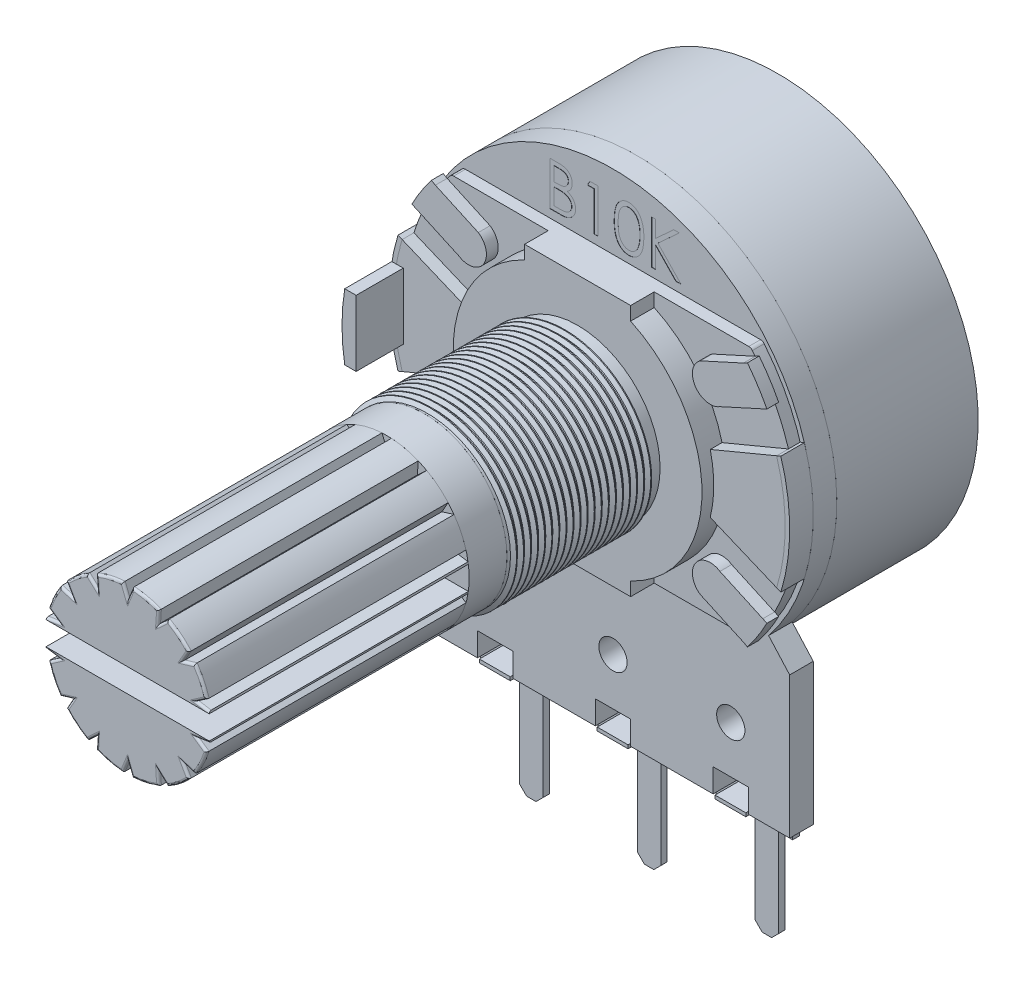
SolidWorks part; units mm, degrees
ref_plane "Alzado" through (0, 0, 0) normal (0, 0, 1) x (1, 0, 0)
ref_plane "Planta" through (0, 0, 0) normal (0, 1, 0) x (1, 0, 0)
ref_plane "Vista lateral" through (0, 0, 0) normal (1, 0, 0) x (0, 0, -1)
sketch "Croquis1" plane through (0, 0, 0) normal (0, 0, 1) x (1, 0, 0)
  circle A0 centre (0, 0) radius 8.5
  dimension "D1" = 17
extrude "Saliente-Extruir1" add sketch "Croquis1" along normal blind 6
sketch "Croquis2" plane through (0, 0, 0) normal (0, 0, -1) x (-1, 0, 0)
  line L0 (0, 0) -> (0, 8.5) construction
  line L1 (0, 0) -> (9.791, 0) construction
  line L2 (6.941, 1) -> (6.941, -1)
  line L3 (6.941, 1) -> (8.441, 1)
  line L4 (6.941, -1) -> (8.441, -1)
  circle A0 centre (0, 0) radius 8.5 construction
  arc A1 (8.441, 1) -> (8.441, -1) centre (0, 0) cw
  point P12 (6.941, 0)
  dimension "D1" = 1
  dimension "D2" = 1.5
extrude "Cortar-Extruir1" cut sketch "Croquis2" against normal blind 3 contours A1 L4 L2 L3
ref_plane "Plano1" through (0, -8.5, 0) normal (0, 1, 0) x (1, 0, 0)
sketch "Croquis3" plane through (0, -8.5, 0) normal (0, 1, 0) x (1, 0, 0)
  line L0 (0, 0) -> (0, -4.2789) construction
  line L1 (0, -4.2789) -> (0, -6) construction
  line L2 (-8.5, -6) -> (8.5, -6) construction
  line L3 (5.5, -3.5) -> (-5.5, -3.5)
  line L4 (-5.5, -3.5) -> (-5.5, -6)
  line L5 (-5.5, -6) -> (5.5, -6)
  line L6 (5.5, -3.5) -> (5.5, -6)
  point P11 (0, -3.5)
  dimension "D1" = 5.5
  dimension "D2" = 2.5
extrude "Cortar-Extruir2" cut sketch "Croquis3" along normal blind 5
sketch "Croquis4" plane through (0, 0, 6) normal (0, 0, 1) x (1, 0, 0)
  line L0 (-7.5, -12.3514) -> (7.5, -12.3514)
  line L1 (7.5, -12.3514) -> (7.5, -6.3514)
  line L2 (-7.5, -12.3514) -> (-7.5, -6.3514)
  line L3 (0, 0) -> (0, -14.8368) construction
  line L5 (6.604, -5.3514) -> (7.5, -6.3514)
  line L7 (-6.604, -5.3514) -> (-7.5, -6.3514)
  arc A0 (6.604, -5.3514) -> (-6.604, -5.3514) centre (0, 0) ccw
  arc A1 (5.5, -6.4807) -> (-5.5, -6.4807) centre (0, 0) ccw construction
  point P11 (0, -12.3514)
  dimension "D1" = 6
  dimension "D2" = 7.5
  dimension "D3" = 7
extrude "Saliente-Extruir2" add sketch "Croquis4" along normal blind 1 separate body
sketch "Croquis5" plane through (0, 0, 7) normal (0, 0, 1) x (1, 0, 0)
  line L0 (6.2625, -5.3514) -> (-6.2625, -5.3514)
  line L1 (0, 0) -> (4.67, 0) construction
  line L2 (6.2625, 5.3514) -> (-6.2625, 5.3514)
  line L3 (0, 8.5) -> (6.3562, 8.5) construction
  line L5 (0, 0) -> (0, 6.7087) construction
  line L6 (0, 0) -> (0, -6.9451) construction
  arc A1 (6.4169, 5.2784) -> (6.4169, -5.2784) centre (0, 0) cw
  arc A2 (6.4169, 5.2784) -> (6.2625, 5.3514) centre (6.2625, 5.1514) ccw
  arc A3 (6.2625, -5.3514) -> (6.4169, -5.2784) centre (6.2625, -5.1514) ccw
  arc A4 (-6.4169, 5.2784) -> (-6.2625, 5.3514) centre (-6.2625, 5.1514) cw
  arc A5 (-6.2625, -5.3514) -> (-6.4169, -5.2784) centre (-6.2625, -5.1514) cw
  arc A6 (-6.4169, 5.2784) -> (-6.4169, -5.2784) centre (0, 0) ccw
  point P9 (0, 5.3514)
  point P27 (0, -5.3514)
  dimension "D1" = 0.2
  dimension "D2" = 0.2
extrude "Saliente-Extruir3" add sketch "Croquis5" along normal blind 0.5 separate body
sketch "Croquis6" plane through (0, 0, 7.5) normal (0, 0, 1) x (1, 0, 0)
  line L0 (0, 0) -> (0, 6.118) construction
  line L1 (0, 0) -> (2.5948, 0) construction
  line L2 (8.124, -2.5) -> (5.1285, -1.25)
  line L6 (5.2787, 0) -> (8.5, 0)
  line L7 (8.124, 2.5) -> (5.1285, 1.25)
  line L8 (-8.124, -2.5) -> (-5.1285, -1.25)
  line L9 (-8.124, 2.5) -> (-5.1285, 1.25)
  arc A1 (6.604, -5.3514) -> (-6.604, -5.3514) centre (0, 0) ccw construction
  arc A3 (8.124, 2.5) -> (8.124, -2.5) centre (0, 0) cw
  arc A4 (-8.124, 2.5) -> (-8.124, -2.5) centre (0, 0) ccw
  arc A5 (5.1285, -1.25) -> (5.1285, 1.25) centre (0, 0) ccw
  arc A6 (-5.1285, -1.25) -> (-5.1285, 1.25) centre (0, 0) cw
  point P4 (5.1285, 0)
  arc M17 (6.4169, -5.2784) -> (6.4169, 5.2784) centre (0, 0) ccw
  arc M21 (-6.4169, 5.2784) -> (-6.4169, -5.2784) centre (0, 0) ccw
  dimension "D2" = 1.25
extrude "Saliente-Extruir4" add sketch "Croquis6" along normal blind 0.5 contours L9 L8 M21 | A5 L6 L7 M17 | A5 L2 L6 M17 region at (6.8677, -0.9571, 7.5) region at (6.8677, 0.9571, 7.5) region at (-6.8677, 0, 7.5)
sketch "Croquis7" plane through (0, 0, 7.5) normal (0, 0, 1) x (1, 0, 0)
  line L0 (0, 5.2787) -> (0, 5.8858) construction
  line L1 (-2.25, 5.3514) -> (2.25, 5.3514)
  line L2 (6.2625, 5.3514) -> (-6.2625, 5.3514) construction
  line L3 (2.25, 5.3514) -> (2.25, 4.7751)
  line L4 (0, 0) -> (0, 3.5555) construction
  line L5 (0, 0) -> (2.9172, 0) construction
  line L6 (-2.25, 5.3514) -> (-2.25, 4.7751)
  line L7 (-2.25, -5.3514) -> (2.25, -5.3514)
  line L8 (2.25, -5.3514) -> (2.25, -4.7751)
  line L9 (-2.25, -5.3514) -> (-2.25, -4.7751)
  arc A0 (-2.25, 4.7751) -> (-2.25, -4.7751) centre (0, 0) ccw
  arc A1 (2.25, -4.7751) -> (2.25, 4.7751) centre (0, 0) ccw
  point P13 (0, 5.3514)
  dimension "D1" = 2.25
extrude "Saliente-Extruir5" add sketch "Croquis7" along normal blind 1
sketch "Croquis8" plane through (0, 0, 7) normal (0, 0, 1) x (1, 0, 0)
  line L0 (0, -5.3514) -> (0, -10.1607) construction
  line L1 (-2.25, -5.3514) -> (2.25, -5.3514) construction
  line L2 (7.5, -9.3514) -> (-1.2858, -9.3514) construction
  line L3 (7.5, -12.3514) -> (7.5, -6.3514) construction
  circle A0 centre (0, -9.3514) radius 0.6
  circle A1 centre (5, -9.3514) radius 0.6
  circle A2 centre (-5, -9.3514) radius 0.6
  dimension "D1" = 1.2
  dimension "D2" = 2
  dimension "D3" = 2
extrude "Cortar-Extruir3" cut sketch "Croquis8" against normal blind 5
sketch "Croquis10" plane through (0, 0, 6) normal (0, 0, -1) x (-1, 0, 0)
  line L0 (0, -12.3514) -> (0, -6.0291) construction
  line L1 (7.5, -12.3514) -> (-7.5, -12.3514) construction
  line L2 (1.625, -9.3514) -> (1.625, -13.3514)
  line L3 (1.625, -13.3514) -> (1.125, -13.3514)
  line L4 (1.125, -13.3514) -> (0.8288, -13.2473)
  line L5 (-1.125, -13.3514) -> (-0.8288, -13.2473)
  line L6 (-1.625, -13.3514) -> (-1.125, -13.3514)
  line L7 (-1.625, -9.3514) -> (-1.625, -13.3514)
  line L8 (0, -9.3514) -> (0.815, -9.3514) construction
  line L21 (6.625, -9.3514) -> (6.625, -13.3514)
  line L22 (6.625, -13.3514) -> (6.125, -13.3514)
  line L23 (6.125, -13.3514) -> (5.8288, -13.2473)
  line L24 (3.875, -13.3514) -> (4.1712, -13.2473)
  line L25 (3.375, -13.3514) -> (3.875, -13.3514)
  line L26 (3.375, -9.3514) -> (3.375, -13.3514)
  line L27 (-3.375, -9.3514) -> (-3.375, -13.3514)
  line L28 (-3.375, -13.3514) -> (-3.875, -13.3514)
  line L29 (-3.875, -13.3514) -> (-4.1712, -13.2473)
  line L30 (-6.125, -13.3514) -> (-5.8288, -13.2473)
  line L31 (-6.625, -13.3514) -> (-6.125, -13.3514)
  line L32 (-6.625, -9.3514) -> (-6.625, -13.3514)
  arc A0 (-1.625, -9.3514) -> (1.625, -9.3514) centre (0, -9.3757) cw
  arc A1 (0.8288, -13.2473) -> (-0.8288, -13.2473) centre (0, -15.6059) ccw
  circle A9 centre (5, -9.3514) radius 0.6
  circle A10 centre (0, -9.3514) radius 0.6
  arc A11 (3.375, -9.3514) -> (6.625, -9.3514) centre (5, -9.3757) cw
  arc A12 (5.8288, -13.2473) -> (4.1712, -13.2473) centre (5, -15.6059) ccw
  arc A14 (-6.625, -9.3514) -> (-3.375, -9.3514) centre (-5, -9.3757) cw
  arc A15 (-4.1712, -13.2473) -> (-5.8288, -13.2473) centre (-5, -15.6059) ccw
  circle A16 centre (-5, -9.3514) radius 0.6
  point P17 (0, -12.9561)
  dimension "D4" = 2.5
  dimension "D1" = 2
  dimension "D2" = 0.5
  dimension "D3" = 1
  dimension "D5" = 2
  dimension "D6" = 2
extrude "Saliente-Extruir6" add sketch "Croquis10" along normal blind 0.3 separate body
sketch "Croquis11" plane through (0, 0, 0) normal (1, 0, 0) x (0, 0, -1)
  line L0 (-5.7, -12.9252) -> (-5.4, -12.9252)
  line L1 (-5.2, -13.1252) -> (-5.2, -17.9252)
  line L3 (-5.7, -12.9252) -> (-5.7, -13.1042)
  line L5 (-5.7, -13.1042) -> (-5.6655, -13.1042)
  line L6 (-5.4655, -13.3042) -> (-5.4655, -17.9252)
  line L7 (-5.4655, -17.9252) -> (-5.2, -17.9252)
  arc A0 (-5.6655, -13.1042) -> (-5.4655, -13.3042) centre (-5.6655, -13.3042) cw
  arc A1 (-5.2, -13.1252) -> (-5.4, -12.9252) centre (-5.4, -13.1252) ccw
  point P12 (-5.2, -12.9252)
  dimension "D3" = 0.2
  dimension "D1" = 5
  dimension "D2" = 0.5
extrude "Saliente-Extruir7" add sketch "Croquis11" along normal blind 0.5 and the other way blind 0.5
pattern_linear "MatrizL1" count 2 spacing 5 along (1, 0, 0) of "Saliente-Extruir7"
pattern_linear "MatrizL2" count 2 spacing 5 along (-1, 0, 0) of "Saliente-Extruir7"
chamfer "Chaflán1" distance 0.3 angle 45 2 edges at (4.5, -17.9252, 5.3328) (5.5, -17.9252, 5.3328)
chamfer "Chaflán2" distance 0.3 angle 45 2 edges at (-0.5, -17.9252, 5.3328) (0.5, -17.9252, 5.3328)
chamfer "Chaflán3" distance 0.3 angle 45 2 edges at (-4.5, -17.9252, 5.3328) (-5.5, -17.9252, 5.3328)
sketch "Croquis12" plane through (0, 0, 7) normal (0, 0, 1) x (1, 0, 0)
  line L0 (0, -12.3514) -> (0, -6.5599) construction
  line L1 (-7.5, -12.3514) -> (7.5, -12.3514) construction
  line L2 (-0.75, -11.3514) -> (0.75, -11.3514)
  line L3 (0.75, -11.3514) -> (0.75, -12.3514)
  line L4 (-0.75, -11.3514) -> (-0.75, -12.3514)
  line L5 (-0.75, -12.3514) -> (0.75, -12.3514)
  line L6 (4.25, -12.3514) -> (5.75, -12.3514)
  line L7 (5.75, -11.3514) -> (5.75, -12.3514)
  line L8 (4.25, -11.3514) -> (5.75, -11.3514)
  line L9 (4.25, -11.3514) -> (4.25, -12.3514)
  line L10 (-5.75, -12.3514) -> (-4.25, -12.3514)
  line L11 (-4.25, -11.3514) -> (-4.25, -12.3514)
  line L12 (-5.75, -11.3514) -> (-4.25, -11.3514)
  line L13 (-5.75, -11.3514) -> (-5.75, -12.3514)
  point P10 (0, -11.3514)
  dimension "D1" = 0.75
  dimension "D2" = 1
  dimension "D3" = 2
  dimension "D4" = 2
extrude "Cortar-Extruir4" cut sketch "Croquis12" against normal through all
sketch "Croquis13" plane through (0, 0, 6) normal (0, 0, 1) x (1, 0, 0)
  line L0 (4.25, -12.3514) -> (4.25, -11.3514)
  line L1 (4.25, -11.3514) -> (5.75, -11.3514)
  line L2 (5.75, -11.3514) -> (5.75, -12.3514)
  line L3 (5.75, -12.3514) -> (4.25, -12.3514)
  line L4 (0.75, -12.3514) -> (-0.75, -12.3514)
  line L5 (-0.75, -12.3514) -> (-0.75, -11.3514)
  line L6 (-0.75, -11.3514) -> (0.75, -11.3514)
  line L7 (0.75, -11.3514) -> (0.75, -12.3514)
  line L8 (-4.25, -12.3514) -> (-5.75, -12.3514)
  line L9 (-5.75, -12.3514) -> (-5.75, -11.3514)
  line L10 (-5.75, -11.3514) -> (-4.25, -11.3514)
  line L11 (-4.25, -11.3514) -> (-4.25, -12.3514)
  dimension "D1" = 3
extrude "Cortar-Extruir5" cut sketch "Croquis13" against normal blind 2
sketch "Croquis14" plane through (0, 0, 6) normal (0, 0, 1) x (1, 0, 0)
  line L0 (4.3314, -12.3514) -> (5.6395, -12.3514)
  line L1 (4.25, -12.3514) -> (5.75, -12.3514) construction
  line L2 (5.6395, -12.3514) -> (5.6395, -12.4982)
  line L3 (5.6395, -12.4982) -> (4.3314, -12.4982)
  line L4 (4.3314, -12.4982) -> (4.3314, -12.3514)
  line L5 (-0.6686, -12.4982) -> (-0.6686, -12.3514)
  line L6 (-0.6686, -12.3514) -> (0.6395, -12.3514)
  line L7 (0.6395, -12.3514) -> (0.6395, -12.4982)
  line L8 (0.6395, -12.4982) -> (-0.6686, -12.4982)
  line L9 (-5.6686, -12.4982) -> (-5.6686, -12.3514)
  line L10 (-5.6686, -12.3514) -> (-4.3605, -12.3514)
  line L11 (-4.3605, -12.3514) -> (-4.3605, -12.4982)
  line L12 (-4.3605, -12.4982) -> (-5.6686, -12.4982)
  dimension "D1" = 3
extrude "Saliente-Extruir8" add sketch "Croquis14" along normal blind 1
sketch "Croquis18" plane through (0, 0, 7.5) normal (0, 0, 1) x (1, 0, 0)
  line L0 (0, 0) -> (12.103, 0) construction
  line L1 (7.3598, -3.8564) -> (5.5397, -3.0275)
  line L2 (6.5371, -5.1289) -> (4.7169, -4.3)
  line L3 (7.3598, -3.8564) -> (7.5336, -3.9364)
  line L4 (6.5371, -5.1289) -> (6.7063, -5.2226)
  arc A0 (6.4169, -5.2784) -> (7.9469, -2.4261) centre (0, 0) ccw construction
  arc A1 (5.5397, -3.0275) -> (4.7169, -4.3) centre (5.1283, -3.6637) ccw
  arc A2 (6.604, -5.3514) -> (-6.604, -5.3514) centre (0, 0) ccw construction
  arc A3 (7.5336, -3.9364) -> (6.7063, -5.2226) centre (0, 0) cw
  dimension "D1" = 2
  dimension "D2" = 1.499
extrude "Saliente-Extruir9" add sketch "Croquis18" along normal blind 0.5
mirror "Simetría2" about plane through (0, 0, 0) normal (0, 1, 0) of "Saliente-Extruir9"
mirror "Simetría3" about plane through (0, 0, 0) normal (1, 0, 0) of "Simetría2"
sketch "Croquis19" plane through (0, 0, 8.5) normal (0, 0, 1) x (1, 0, 0)
  circle A0 centre (0, 0) radius 3.5
  dimension "D1" = 7
extrude "Saliente-Extruir10" add sketch "Croquis19" along normal blind 6.5
thread "Rosca1" pitch 0.3 method extrude profile "Perfil de rosca1" start angle 0, offset 0, length 6, pitch 0.3, diameter 7
ref_plane "Plano3" through (-3.5, 0, 15) normal (0, -1, 0) x (-1, 0, 0)
sketch "Perfil de rosca1" plane through (-3.5, 0, 15) normal (0, -1, 0) x (-1, 0, 0)
  line L0 (0, 0) -> (0, 0.3) construction
  line L1 (0, 0) -> (0.1624, 0.0937)
  line L2 (0.1624, 0.0937) -> (0.1624, 0.1312)
  line L3 (0.1624, 0.1312) -> (0, 0.225)
  line L4 (0.1624, 0.1125) -> (0, 0.1125) construction
  line L11 (0, 0) -> (0, 0.225)
  point P2 (0, 0)
  dimension "Pitch" = 0.3
  dimension "Profile_Angle" = 60
  dimension "Profile_Land" = 0.0375
  dimension "Profile_Height" = 0.1624
sketch "Croquis28" plane through (0, 0, 15) normal (0, 0, 1) x (1, 0, 0)
  circle A0 centre (0, 0) radius 3.5
extrude "Saliente-Extruir11" add sketch "Croquis28" along normal blind 1.6 separate body
sketch "Croquis29" plane through (0, 0, 16.6) normal (0, 0, 1) x (1, 0, 0)
  circle A0 centre (0, 0) radius 3.5
extrude "Saliente-Extruir12" add sketch "Croquis29" along normal blind 11 separate body
sketch "Croquis30" plane through (0, 0, 27.6) normal (0, 0, 1) x (1, 0, 0)
  line L0 (0, 0) -> (3.5, 0) construction
  line L1 (-3.4641, 0.5) -> (3.4641, 0.5)
  line L2 (-3.4641, -0.5) -> (3.4641, -0.5)
  arc A0 (-3.4641, 0.5) -> (-3.4641, -0.5) centre (0, 0) ccw
  arc A1 (3.4641, -0.5) -> (3.4641, 0.5) centre (0, 0) ccw
  dimension "D1" = 0.5
extrude "Cortar-Extruir7" cut sketch "Croquis30" against normal blind 11 contours L1 A1 L2 A0
sketch "Croquis32" plane through (0, 0, 27.6) normal (0, 0, 1) x (1, 0, 0)
  line L0 (0, 0) -> (0, 3.5) construction
  line L1 (1.2992, 2.6978) -> (1.3359, 3.235)
  line L2 (0.2, 3.4943) -> (0, 2.9943)
  line L3 (0, 2.9943) -> (-0.2, 3.4943)
  line L4 (1.6963, 3.0615) -> (1.2992, 2.6978)
  line L5 (2.341, 1.8669) -> (2.6072, 2.335)
  line L6 (2.8566, 2.0223) -> (2.341, 1.8669)
  line L7 (2.9192, 0.6663) -> (3.3622, 0.9725)
  line L8 (3.4512, 0.5826) -> (2.9192, 0.6663)
  line L9 (2.9192, -0.6663) -> (3.4512, -0.5826)
  line L10 (3.3622, -0.9725) -> (2.9192, -0.6663)
  line L11 (2.341, -1.8669) -> (2.8566, -2.0223)
  line L12 (2.6072, -2.335) -> (2.341, -1.8669)
  line L13 (1.2992, -2.6978) -> (1.6963, -3.0615)
  line L14 (1.3359, -3.235) -> (1.2992, -2.6978)
  line L15 (0, -2.9943) -> (0.2, -3.4943)
  line L16 (-0.2, -3.4943) -> (0, -2.9943)
  line L17 (-1.2992, -2.6978) -> (-1.3359, -3.235)
  line L18 (-1.6963, -3.0615) -> (-1.2992, -2.6978)
  line L19 (-2.341, -1.8669) -> (-2.6072, -2.335)
  line L20 (-2.8566, -2.0223) -> (-2.341, -1.8669)
  line L21 (-2.9192, -0.6663) -> (-3.3622, -0.9725)
  line L22 (-3.4512, -0.5826) -> (-2.9192, -0.6663)
  line L23 (-2.9192, 0.6663) -> (-3.4512, 0.5826)
  line L24 (-3.3622, 0.9725) -> (-2.9192, 0.6663)
  line L25 (-2.341, 1.8669) -> (-2.8566, 2.0223)
  line L26 (-2.6072, 2.335) -> (-2.341, 1.8669)
  line L27 (-1.2992, 2.6978) -> (-1.6963, 3.0615)
  line L28 (-1.3359, 3.235) -> (-1.2992, 2.6978)
  arc A0 (0.2, 3.4943) -> (-0.2, 3.4943) centre (0, 0) ccw
  arc A1 (1.6963, 3.0615) -> (1.3359, 3.235) centre (0, 0) ccw
  arc A2 (2.8566, 2.0223) -> (2.6072, 2.335) centre (0, 0) ccw
  arc A3 (3.4512, 0.5826) -> (3.3622, 0.9725) centre (0, 0) ccw
  arc A4 (3.3622, -0.9725) -> (3.4512, -0.5826) centre (0, 0) ccw
  arc A5 (2.6072, -2.335) -> (2.8566, -2.0223) centre (0, 0) ccw
  arc A6 (1.3359, -3.235) -> (1.6963, -3.0615) centre (0, 0) ccw
  arc A7 (-0.2, -3.4943) -> (0.2, -3.4943) centre (0, 0) ccw
  arc A8 (-1.6963, -3.0615) -> (-1.3359, -3.235) centre (0, 0) ccw
  arc A9 (-2.8566, -2.0223) -> (-2.6072, -2.335) centre (0, 0) ccw
  arc A10 (-3.4512, -0.5826) -> (-3.3622, -0.9725) centre (0, 0) ccw
  arc A11 (-3.3622, 0.9725) -> (-3.4512, 0.5826) centre (0, 0) ccw
  arc A12 (-2.6072, 2.335) -> (-2.8566, 2.0223) centre (0, 0) ccw
  arc A13 (-1.3359, 3.235) -> (-1.6963, 3.0615) centre (0, 0) ccw
  point P48 (0, 0)
  dimension "D5" = 7
  dimension "D1" = 14
  dimension "D2" = 0.5
  dimension "D3" = 0.2
  dimension "D4" = 0.2
extrude "Cortar-Extruir8" cut sketch "Croquis32" against normal blind 11
fillet "Redondeo1" radius 0.1 20 edges at (0.7788, 3.4122, 27.6) (1.3175, 2.9664, 27.6) (1.4977, 2.8796, 27.6) (2.1822, 2.7364, 27.6) (2.4741, 2.101, 27.6) (2.5988, 1.9446, 27.6) (3.1534, 1.5186, 27.6) (3.1407, 0.8194, 27.6) (3.1852, 0.6244, 27.6) (-3.1852, 0.6244, 27.6) (-3.1407, 0.8194, 27.6) (-3.1534, 1.5186, 27.6) (-2.5988, 1.9446, 27.6) (-2.4741, 2.101, 27.6) (-2.1822, 2.7364, 27.6) (-1.4977, 2.8796, 27.6) (-1.3175, 2.9664, 27.6) (-0.7788, 3.4122, 27.6) (-0.1, 3.2443, 27.6) (0.1, 3.2443, 27.6)
fillet "Redondeo2" radius 0.1 20 edges at (3.1852, -0.6244, 27.6) (3.1407, -0.8194, 27.6) (3.1534, -1.5186, 27.6) (2.5988, -1.9446, 27.6) (2.4741, -2.101, 27.6) (2.1822, -2.7364, 27.6) (0.7788, -3.4122, 27.6) (1.4977, -2.8796, 27.6) (1.3175, -2.9664, 27.6) (0.1, -3.2443, 27.6) (-0.1, -3.2443, 27.6) (-0.7788, -3.4122, 27.6) (-1.3175, -2.9664, 27.6) (-1.4977, -2.8796, 27.6) (-2.1822, -2.7364, 27.6) (-2.4741, -2.101, 27.6) (-2.5988, -1.9446, 27.6) (-3.1852, -0.6244, 27.6) (-3.1407, -0.8194, 27.6) (-3.1534, -1.5186, 27.6)
sketch "Croquis33" plane through (0, 0, 7) normal (0, 0, 1) x (1, 0, 0)
  line L0 (-2.9162, 5.7003) -> (2.4725, 5.7003) construction
  text T0 "B10K" font "Century Gothic" height in points 7
extrude "Cortar-Extruir9" cut sketch "Croquis33" against normal blind 0.01
sketch "Croquis34" plane through (0, 0, 8) normal (0, 0, 1) x (1, 0, 0)
  line L0 (-7.9, 1.4) -> (-7.9, -1.4)
  line L1 (-8.5, 0) -> (-8.5, 4.0626) construction
  line L2 (-7.9, -1.4) -> (-8.3839, -1.4)
  line L3 (-7.9, 1.4) -> (-8.3839, 1.4)
  arc A0 (6.604, -5.3514) -> (-6.604, -5.3514) centre (0, 0) ccw construction
  arc A1 (-8.3839, 1.4) -> (-8.3839, -1.4) centre (0, 0) ccw
  point P7 (-7.9, 0)
  dimension "D1" = 1.2
  dimension "D2" = 2.8
extrude "Saliente-Extruir13" add sketch "Croquis34" along normal blind 2
sketch "Croquis9" plane through (0, 0, 7) normal (0, 0, 1) x (1, 0, 0)
  line L0 (7.9469, 2.4261) -> (8.1243, 2.4992)
  line L1 (0, 0) -> (9.2831, 0) construction
  line L2 (0, 0) -> (0, 4.4743) construction
  line L3 (7.9469, -2.4261) -> (8.1243, -2.4992)
  line L4 (-7.9469, -2.4261) -> (-8.1243, -2.4992)
  line L5 (-7.9469, 2.4261) -> (-8.1243, 2.4992)
  arc A0 (6.604, -5.3514) -> (-6.604, -5.3514) centre (0, 0) ccw construction
  arc A1 (-8.1243, 2.4992) -> (-8.1243, -2.4992) centre (0, 0) ccw
  arc A2 (7.9469, 2.4261) -> (7.9469, -2.4261) centre (0, 0) cw
  arc A3 (-7.9469, 2.4261) -> (-7.9469, -2.4261) centre (0, 0) ccw
  arc A4 (8.1243, 2.4992) -> (8.1243, -2.4992) centre (0, 0) cw
extrude "Saliente-Extruir14" add sketch "Croquis9" along normal blind 1 separate body
sketch "Croquis35" plane through (0, 0, 0) normal (0, 0, -1) x (-1, 0, 0)
  line L0 (-5.5885, 1.863) -> (6.9577, 1.863) construction
  line L1 (-3.6359, -2.3363) -> (5.4957, -2.3363) construction
  text T0 "ALPHA" font "Century Gothic" height in points 10
  text T1 "B10K" font "Century Gothic" height in points 10
extrude "Cortar-Extruir10" cut sketch "Croquis35" against normal blind 0.01
